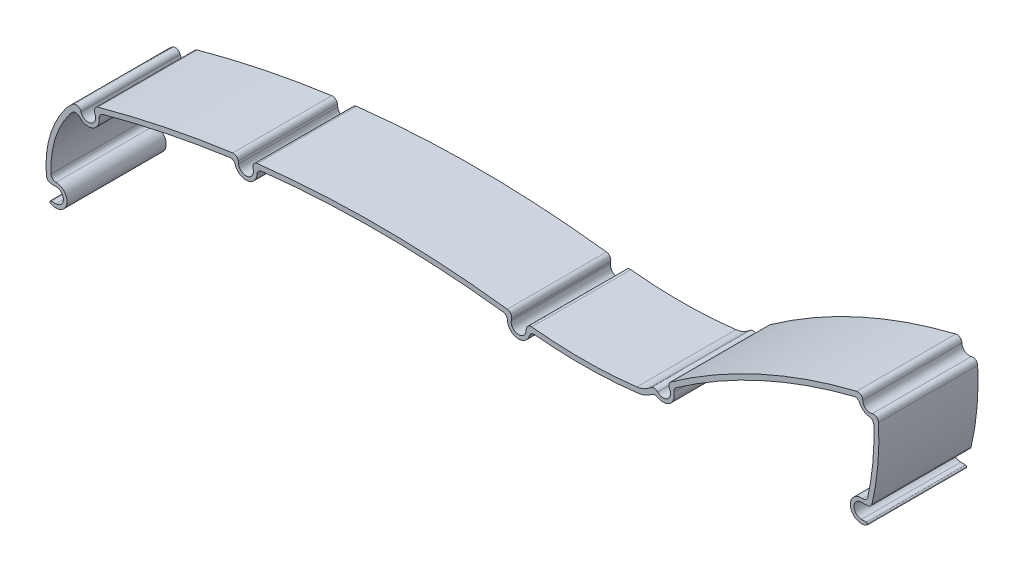
SolidWorks part; units mm, degrees
material "ｴﾎﾟｷｼ樹脂(充填剤なし)"
ref_plane "正面" through (0, 0, 0) normal (0, 0, 1) x (1, 0, 0)
ref_plane "平面" through (0, 0, 0) normal (0, 1, 0) x (1, 0, 0)
ref_plane "右側面" through (0, 0, 0) normal (1, 0, 0) x (0, 0, -1)
sketch "ｽｹｯﾁ1" plane through (0, 0, 0) normal (0, 0, 1) x (1, 0, 0)
  line L0 (152.9752, 59.7355) -> (155.8598, 58.9115) construction
  line L2 (-22.5, -19) -> (22.5, -19)
  line L3 (147, 0) -> (148, 0)
  line L21 (148, 0) -> (148, 15)
  line L23 (148, 15) -> (147, 15)
  circle A0 centre (152.9752, 59.7355) radius 3 construction
  arc A25 (145.1217, 33.8719) -> (159.4857, 98.9896) centre (52.35, 88.479) ccw
  arc A26 (159.4857, 98.9896) -> (155.8531, 101.6261) centre (156.5, 98.6967) ccw
  arc A27 (155.8531, 101.6261) -> (74.5652, 65.2106) centre (203.2901, -113.1988) ccw
  arc A28 (73.7195, 65.056) -> (74.5652, 65.2106) centre (73.98, 66.0215) ccw
  arc A29 (73.7195, 65.056) -> (74.5652, 65.2106) centre (73.98, 66.0215) ccw
  arc A30 (73.7195, 65.056) -> (69.9392, 62.246) centre (72.938, 62.1596) ccw
  arc A31 (73.7195, 65.056) -> (69.9392, 62.246) centre (72.938, 62.1596) ccw
  arc A32 (62.3481, 57.6959) -> (67.3326, 59.7624) centre (61.1527, 67.6242) ccw
  arc A33 (15.0718, 58.0612) -> (62.3481, 57.6959) centre (40.1338, 242.1889) ccw
  arc A34 (15.0718, 58.0612) -> (-159.8291, 45.3832) centre (-42.29, -363.3692) ccw
  arc A35 (-159.8291, 45.3832) -> (-168.029, 39.7531) centre (-155.4945, 30.2837) ccw
  arc A36 (-168.029, 39.7531) -> (-174.9177, 6.802) centre (-136.5587, 15.9784) ccw
  arc A37 (-174.9177, 6.802) -> (-172, 4.5) centre (-172, 7.5) ccw
  arc A38 (-128.5711, -10.4869) -> (-172, 4.5) centre (-172, -65.9175) ccw
  arc A39 (-128.5711, -10.4869) -> (-89, -16.1206) centre (-103.9017, 21) ccw
  arc A40 (-24.2684, -18.5879) -> (-89, -16.1206) centre (-59.3978, -89.8605) ccw
  arc A41 (-24.2684, -18.5879) -> (-22.5, -19) centre (-22.5, -15) ccw
  arc A42 (95.4808, -24.1793) -> (22.5, -19) centre (22.5, -535.7727) ccw
  arc A43 (95.4808, -24.1793) -> (100, -24.5) centre (100, 7.5) ccw
  arc A44 (100, -24.5) -> (140.9896, -3.1331) centre (100, 25.5) ccw
  arc A45 (147, 0) -> (140.9896, -3.1331) centre (147, -7.3316) ccw
  arc A48 (69.5475, 61.4807) -> (69.9392, 62.246) centre (68.9396, 62.2747) ccw
  arc A49 (145.1217, 33.8719) -> (140.5409, 25.3936) centre (258.447, -32.8336) ccw
  arc A50 (155.8598, 58.9115) -> (159.4857, 98.9896) centre (52.35, 88.479) ccw
  arc A51 (159.4857, 98.9896) -> (155.8531, 101.6261) centre (156.5, 98.6967) ccw
  arc A52 (155.8531, 101.6261) -> (74.5652, 65.2106) centre (203.2901, -113.1988) ccw
  arc A53 (69.5475, 61.4807) -> (69.9392, 62.246) centre (68.9396, 62.2747) ccw
  arc A54 (69.5475, 61.4807) -> (67.3326, 59.7624) centre (203.2901, -113.1988) ccw
  arc A55 (69.5475, 61.4807) -> (67.3326, 59.7624) centre (203.2901, -113.1988) ccw
  arc A56 (140.5409, 25.3936) -> (147, 15) centre (147, 22.2038) ccw
  arc A57 (62.3481, 57.6959) -> (67.3326, 59.7624) centre (61.1527, 67.6242) ccw
  arc A58 (15.0718, 58.0612) -> (62.3481, 57.6959) centre (40.1338, 242.1889) ccw
  arc A59 (15.0718, 58.0612) -> (-159.8291, 45.3832) centre (-42.29, -363.3692) ccw
  arc A60 (-159.8291, 45.3832) -> (-168.029, 39.7531) centre (-155.4945, 30.2837) ccw
  arc A61 (-168.029, 39.7531) -> (-174.9177, 6.802) centre (-136.5587, 15.9784) ccw
  dimension "D1" = 0
extrude "押し出し-薄板1" add sketch "ｽｹｯﾁ1" along normal up to surface (40 mm away) thin thin type one direction reverse wall 2
sketch "ｽｹｯﾁ2" plane through (0, 0, 0) normal (0, 0, 1) x (1, 0, 0)
  circle A0 centre (156.5, 98.6967) radius 3 construction
  circle A1 centre (152.9752, 59.7355) radius 3 construction
  circle A2 centre (72.938, 62.1596) radius 3 construction
  circle A3 centre (14.6672, 55.0886) radius 3 construction
  circle A4 centre (-95.3328, 55.6027) radius 3 construction
  circle A5 centre (-159, 42.5) radius 3 construction
  circle A6 centre (-172, 7.5) radius 3 construction
  circle A7 centre (156.5, 98.6967) radius 3
  circle A8 centre (152.9752, 59.7355) radius 3
  circle A9 centre (72.938, 62.1596) radius 3
  circle A10 centre (14.6672, 55.0886) radius 3
  circle A11 centre (-95.3328, 55.6027) radius 3
  circle A12 centre (-159, 42.5) radius 3
  circle A13 centre (-172, 7.5) radius 3
extrude "ﾎﾞｽ - 押し出し1" add sketch "ｽｹｯﾁ2" along normal through all
sketch "ｽｹｯﾁ3" plane through (0, 0, 40) normal (0, 0, 1) x (1, 0, 0)
  circle A0 centre (-172, 7.5) radius 4.5
  circle A1 centre (-159, 42.5) radius 4.5
  circle A2 centre (-95.3328, 55.6027) radius 4.5
  circle A3 centre (14.6672, 55.0886) radius 4.5
  circle A4 centre (72.938, 62.1596) radius 4.5
  circle A5 centre (156.5, 98.6967) radius 4.5
  circle A6 centre (152.9752, 59.7355) radius 4.5
  arc A37 (-168.029, 39.7531) -> (-174.9177, 6.802) centre (-136.5587, 15.9784) ccw
  arc A38 (-174.9177, 6.802) -> (-173.5323, 10.0791) centre (-172, 7.5) ccw
  arc A39 (-166.4332, 38.5475) -> (-173.5323, 10.0791) centre (-136.5587, 15.9784) ccw
  arc A40 (-161.9964, 42.3531) -> (-166.4332, 38.5475) centre (-155.4945, 30.2837) ccw
  arc A41 (-161.9964, 42.3531) -> (-156.5523, 44.2345) centre (-159, 42.5) ccw
  arc A42 (-98.2666, 56.2298) -> (-156.5523, 44.2345) centre (-42.29, -363.3692) ccw
  arc A43 (-98.2666, 56.2298) -> (-92.6479, 56.9411) centre (-95.3328, 55.6027) ccw
  arc A44 (11.9949, 56.452) -> (-92.6479, 56.9411) centre (-42.29, -363.3692) ccw
  arc A45 (11.9949, 56.452) -> (17.6, 55.72) centre (14.6672, 55.0886) ccw
  arc A46 (17.6, 55.72) -> (62.5872, 55.7103) centre (40.1338, 242.1889) ccw
  arc A47 (62.5872, 55.7103) -> (68.5686, 58.19) centre (61.1527, 67.6242) ccw
  arc A48 (70.7634, 59.8927) -> (68.5686, 58.19) centre (203.2901, -113.1988) ccw
  arc A49 (70.7634, 59.8927) -> (70.8745, 59.982) centre (68.9396, 62.2747) ccw
  arc A50 (70.8745, 59.982) -> (75.6179, 63.508) centre (72.938, 62.1596) ccw
  arc A51 (75.6179, 63.508) -> (75.7354, 63.5887) centre (73.98, 66.0215) ccw
  arc A52 (153.5202, 99.0439) -> (75.7354, 63.5887) centre (203.2901, -113.1988) ccw
  arc A53 (153.5202, 99.0439) -> (157.7346, 95.9625) centre (156.5, 98.6967) ccw
  arc A54 (154.6805, 62.2037) -> (157.7346, 95.9625) centre (52.35, 88.479) ccw
  arc A55 (154.6805, 62.2037) -> (155.8598, 58.9115) centre (152.9752, 59.7355) ccw
  arc A56 (155.8598, 58.9115) -> (159.4857, 98.9896) centre (52.35, 88.479) ccw
  arc A57 (159.4857, 98.9896) -> (155.8531, 101.6261) centre (156.5, 98.6967) ccw
  arc A58 (155.8531, 101.6261) -> (74.5652, 65.2106) centre (203.2901, -113.1988) ccw
  arc A59 (73.7195, 65.056) -> (74.5652, 65.2106) centre (73.98, 66.0215) ccw
  arc A60 (73.7195, 65.056) -> (69.9392, 62.246) centre (72.938, 62.1596) ccw
  arc A61 (69.5475, 61.4807) -> (69.9392, 62.246) centre (68.9396, 62.2747) ccw
  arc A62 (69.5475, 61.4807) -> (67.3326, 59.7624) centre (203.2901, -113.1988) ccw
  arc A63 (62.3481, 57.6959) -> (67.3326, 59.7624) centre (61.1527, 67.6242) ccw
  arc A64 (15.0718, 58.0612) -> (62.3481, 57.6959) centre (40.1338, 242.1889) ccw
  arc A65 (15.0718, 58.0612) -> (-159.8291, 45.3832) centre (-42.29, -363.3692) ccw
  arc A66 (-159.8291, 45.3832) -> (-168.029, 39.7531) centre (-155.4945, 30.2837) ccw
  arc A67 (-168.029, 39.7531) -> (-174.9177, 6.802) centre (-136.5587, 15.9784) ccw
  arc A68 (-174.9177, 6.802) -> (-173.5323, 10.0791) centre (-172, 7.5) ccw
  arc A69 (-166.4332, 38.5475) -> (-173.5323, 10.0791) centre (-136.5587, 15.9784) ccw
  arc A70 (-161.9964, 42.3531) -> (-166.4332, 38.5475) centre (-155.4945, 30.2837) ccw
  arc A71 (-161.9964, 42.3531) -> (-156.5523, 44.2345) centre (-159, 42.5) ccw
  arc A72 (-98.2666, 56.2298) -> (-156.5523, 44.2345) centre (-42.29, -363.3692) ccw
  arc A73 (-98.2666, 56.2298) -> (-92.6479, 56.9411) centre (-95.3328, 55.6027) ccw
  arc A74 (11.9949, 56.452) -> (-92.6479, 56.9411) centre (-42.29, -363.3692) ccw
  arc A75 (11.9949, 56.452) -> (17.6, 55.72) centre (14.6672, 55.0886) ccw
  arc A76 (17.6, 55.72) -> (62.5872, 55.7103) centre (40.1338, 242.1889) ccw
  arc A77 (62.5872, 55.7103) -> (68.5686, 58.19) centre (61.1527, 67.6242) ccw
  arc A78 (70.7634, 59.8927) -> (68.5686, 58.19) centre (203.2901, -113.1988) ccw
  arc A79 (70.7634, 59.8927) -> (70.8745, 59.982) centre (68.9396, 62.2747) ccw
  arc A80 (70.8745, 59.982) -> (75.6179, 63.508) centre (72.938, 62.1596) ccw
  arc A81 (75.6179, 63.508) -> (75.7354, 63.5887) centre (73.98, 66.0215) ccw
  arc A82 (153.5202, 99.0439) -> (75.7354, 63.5887) centre (203.2901, -113.1988) ccw
  arc A83 (153.5202, 99.0439) -> (157.7346, 95.9625) centre (156.5, 98.6967) ccw
  arc A84 (154.6805, 62.2037) -> (157.7346, 95.9625) centre (52.35, 88.479) ccw
  arc A85 (154.6805, 62.2037) -> (155.8598, 58.9115) centre (152.9752, 59.7355) ccw
  arc A86 (155.8598, 58.9115) -> (159.4857, 98.9896) centre (52.35, 88.479) ccw
  arc A87 (159.4857, 98.9896) -> (155.8531, 101.6261) centre (156.5, 98.6967) ccw
  arc A88 (155.8531, 101.6261) -> (74.5652, 65.2106) centre (203.2901, -113.1988) ccw
  arc A89 (73.7195, 65.056) -> (74.5652, 65.2106) centre (73.98, 66.0215) ccw
  arc A90 (73.7195, 65.056) -> (69.9392, 62.246) centre (72.938, 62.1596) ccw
  arc A91 (69.5475, 61.4807) -> (69.9392, 62.246) centre (68.9396, 62.2747) ccw
  arc A92 (69.5475, 61.4807) -> (67.3326, 59.7624) centre (203.2901, -113.1988) ccw
  arc A93 (62.3481, 57.6959) -> (67.3326, 59.7624) centre (61.1527, 67.6242) ccw
  arc A94 (15.0718, 58.0612) -> (62.3481, 57.6959) centre (40.1338, 242.1889) ccw
  arc A95 (15.0718, 58.0612) -> (-159.8291, 45.3832) centre (-42.29, -363.3692) ccw
  arc A96 (-159.8291, 45.3832) -> (-168.029, 39.7531) centre (-155.4945, 30.2837) ccw
  arc M31 (-168.029, 39.7531) -> (-174.9177, 6.802) centre (-136.5587, 15.9784) ccw
  arc M32 (-174.9177, 6.802) -> (-173.5323, 10.0791) centre (-172, 7.5) ccw
  arc M33 (-173.5323, 10.0791) -> (-166.4332, 38.5475) centre (-136.5587, 15.9784) cw
  arc M34 (-166.4332, 38.5475) -> (-161.9964, 42.3531) centre (-155.4945, 30.2837) cw
  arc M35 (-161.9964, 42.3531) -> (-156.5523, 44.2345) centre (-159, 42.5) ccw
  arc M36 (-156.5523, 44.2345) -> (-98.2666, 56.2298) centre (-42.29, -363.3692) cw
  arc M37 (-98.2666, 56.2298) -> (-92.6479, 56.9411) centre (-95.3328, 55.6027) ccw
  arc M38 (-92.6479, 56.9411) -> (11.9949, 56.452) centre (-42.29, -363.3692) cw
  arc M39 (11.9949, 56.452) -> (17.6, 55.72) centre (14.6672, 55.0886) ccw
  arc M40 (17.6, 55.72) -> (62.5872, 55.7103) centre (40.1338, 242.1889) ccw
  arc M42 (68.5686, 58.19) -> (70.7634, 59.8927) centre (203.2901, -113.1988) cw
  arc M43 (70.7634, 59.8927) -> (70.8745, 59.982) centre (68.9396, 62.2747) ccw
  arc M44 (70.8745, 59.982) -> (75.6179, 63.508) centre (72.938, 62.1596) ccw
  arc M45 (75.6179, 63.508) -> (75.7354, 63.5887) centre (73.98, 66.0215) ccw
  arc M46 (75.7354, 63.5887) -> (153.5202, 99.0439) centre (203.2901, -113.1988) cw
  arc M47 (153.5202, 99.0439) -> (157.7346, 95.9625) centre (156.5, 98.6967) ccw
  arc M48 (157.7346, 95.9625) -> (154.6805, 62.2037) centre (52.35, 88.479) cw
  arc M49 (154.6805, 62.2037) -> (155.8598, 58.9115) centre (152.9752, 59.7355) ccw
  arc M50 (155.8598, 58.9115) -> (159.4857, 98.9896) centre (52.35, 88.479) ccw
  dimension "D1" = 9
  dimension "D2" = 0
extrude "ﾎﾞｽ - 押し出し2" add sketch "ｽｹｯﾁ3" against normal through all contours A6 M48 M50 M49 | A5 M46 M48 M47 | A4 M42 M46 M45 M44 M43 | A3 M38 M40 M39 | A2 M36 M38 M37 | A1 M34 M36 M35 | A0 M31 M33 M32 region at (-173.3991, 3.3572, 40) region at (-162.6457, 41.8498, 40) region at (-99.0256, 56.0185, 40) region at (11.207, 56.4437, 40) region at (70.2831, 59.3943, 40) region at (154.6043, 96.1097, 40) region at (154.749, 62.9939, 40)
sketch "ｽｹｯﾁ4" plane through (0, 0, 40) normal (0, 0, 1) x (1, 0, 0)
  line L0 (-159, 42.5) -> (-159.8361, 45.3811) construction
  line L1 (-161.8811, 41.6639) -> (-162.7173, 44.545)
  line L2 (-156.1189, 43.3361) -> (-156.955, 46.2173)
  line L3 (-172, 7.5) -> (-176.5, 7.5) construction
  line L4 (-172, 4.5) -> (-176.5, 4.5)
  line L5 (-172, 10.5) -> (-176.5, 10.5)
  line L6 (-95.3328, 55.6027) -> (-95.7096, 58.579) construction
  line L7 (-98.3091, 55.2259) -> (-98.6859, 58.2022)
  line L8 (-92.3566, 55.9795) -> (-92.7334, 58.9558)
  line L9 (14.6672, 55.0886) -> (15.0718, 58.0612) construction
  line L10 (11.6946, 55.4932) -> (12.0992, 58.4658)
  line L11 (17.6397, 54.684) -> (18.0444, 57.6566)
  line L12 (72.938, 62.1596) -> (71.1482, 64.5673) construction
  line L13 (70.5303, 60.3699) -> (68.7406, 62.7776)
  line L14 (75.3456, 63.9494) -> (73.5559, 66.357)
  line L15 (156.5, 98.6967) -> (158.2622, 101.1246) construction
  line L16 (154.0721, 100.4589) -> (155.8343, 102.8868)
  line L17 (158.9279, 96.9345) -> (160.6901, 99.3624)
  line L18 (152.9752, 59.7355) -> (157.4752, 59.7355) construction
  line L19 (152.9752, 62.7355) -> (157.4752, 62.7355)
  line L20 (152.9752, 56.7355) -> (157.4752, 56.7355)
  line L21 (-99.8134, 56.0205) -> (-91.0978, 57.1239) construction
  arc A0 (15.0718, 58.0612) -> (-159.8291, 45.3832) centre (-42.29, -363.3692) ccw construction
  arc A1 (-159.8291, 45.3832) -> (-168.029, 39.7531) centre (-155.4945, 30.2837) ccw construction
  arc A2 (-161.8811, 41.6639) -> (-156.1189, 43.3361) centre (-159, 42.5) ccw
  arc A3 (-156.955, 46.2173) -> (-162.7173, 44.545) centre (-159.8361, 45.3811) ccw
  arc A4 (-172, 4.5) -> (-172, 10.5) centre (-172, 7.5) ccw
  arc A5 (-176.5, 10.5) -> (-176.5, 4.5) centre (-176.5, 7.5) ccw
  arc A6 (-98.3091, 55.2259) -> (-92.3566, 55.9795) centre (-95.3328, 55.6027) ccw
  arc A7 (-92.7334, 58.9558) -> (-98.6859, 58.2022) centre (-95.7096, 58.579) ccw
  arc A8 (15.0718, 58.0612) -> (62.3481, 57.6959) centre (40.1338, 242.1889) ccw construction
  arc A9 (11.6946, 55.4932) -> (17.6397, 54.684) centre (14.6672, 55.0886) ccw
  arc A10 (18.0444, 57.6566) -> (12.0992, 58.4658) centre (15.0718, 58.0612) ccw
  arc A11 (73.7195, 65.056) -> (69.9392, 62.246) centre (72.938, 62.1596) ccw construction
  arc A12 (70.5303, 60.3699) -> (75.3456, 63.9494) centre (72.938, 62.1596) ccw
  arc A13 (73.5559, 66.357) -> (68.7406, 62.7776) centre (71.1482, 64.5673) ccw
  arc A14 (159.4857, 98.9896) -> (155.8531, 101.6261) centre (156.5, 98.6967) ccw construction
  arc A15 (154.0721, 100.4589) -> (158.9279, 96.9345) centre (156.5, 98.6967) ccw
  arc A16 (160.6901, 99.3624) -> (155.8343, 102.8868) centre (158.2622, 101.1246) ccw
  arc A17 (155.0589, 63.7241) -> (156.7424, 62.1969) centre (152.9752, 59.7355) ccw construction
  arc A18 (152.9752, 62.7355) -> (152.9752, 56.7355) centre (152.9752, 59.7355) ccw
  arc A19 (157.4752, 56.7355) -> (157.4752, 62.7355) centre (157.4752, 59.7355) ccw
  arc A20 (-175.5786, 10.2283) -> (-173.7486, 11.6464) centre (-172, 7.5) ccw construction
  point P12 (-159.4181, 43.9406)
  point P19 (-174.25, 7.5)
  point P29 (-95.5212, 57.0909)
  point P37 (14.8695, 56.5749)
  point P48 (72.0431, 63.3635)
  point P59 (157.3811, 99.9106)
  point P70 (155.2252, 59.7355)
  dimension "D1" = 6
extrude "ｶｯﾄ - 押し出し2" cut sketch "ｽｹｯﾁ4" against normal through all
fillet "ﾌｨﾚｯﾄ1" radius 2 24 edges at (-173.7486, 11.6464, 20) (-155.0485, 44.6531, 20) (-99.8134, 56.0205, 20) (-91.0978, 57.1239, 20) (10.4465, 56.6493, 20) (19.1445, 55.5398, 20) (69.6787, 59.0569, 20) (76.8484, 64.3864, 20) (152, 98.6817, 20) (157.834, 94.399, 20) (155.0589, 63.7241, 20) (156.8765, 62.7355, 20) (159.5915, 97.8487, 20) (154.7384, 101.3769, 20) (74.4582, 65.1432, 20) (69.6428, 61.5638, 20) (18.0475, 57.6806, 20) (12.0977, 58.4553, 20) (-92.7321, 58.9453, 20) (-98.6846, 58.1917, 20) (-156.95, 46.2001, 20) (-162.6387, 44.2745, 20) (-175.6177, 10.5, 20) (-163.3861, 41.4939, 20)
fillet "ﾌｨﾚｯﾄ2" radius 0.5 2 edges at (156.3293, 56.7355, 20) (-175.3541, 4.5, 20)
